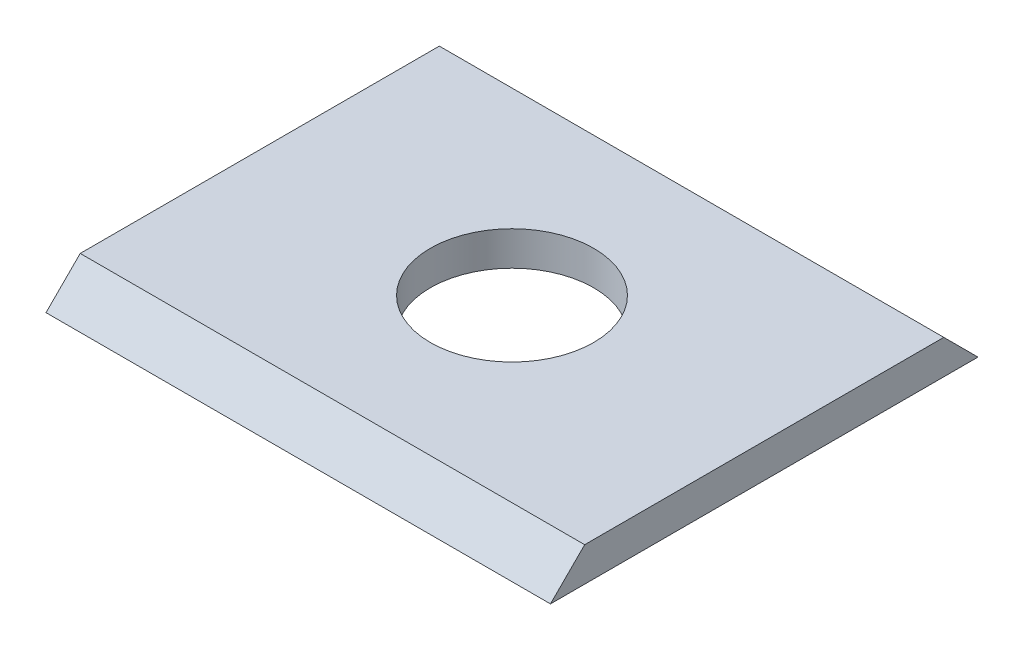
SolidWorks part; units mm, degrees
ref_plane "Front Plane" through (0, 0, 0) normal (0, 0, 1) x (1, 0, 0)
ref_plane "Top Plane" through (0, 0, 0) normal (0, 1, 0) x (1, 0, 0)
ref_plane "Right Plane" through (0, 0, 0) normal (1, 0, 0) x (0, 0, -1)
sketch "Sketch1" plane through (0, 0, 0) normal (0, 1, 0) x (1, 0, 0)
  line L0 (0, 0) -> (0, 50)
  line L1 (0, 0) -> (59, 0)
  line L2 (59, 0) -> (59, 50)
  line L3 (59, 50) -> (0, 50)
  line L4 (29.5, 50) -> (29.5, 25)
  circle A0 centre (29.5, 25) radius 9.55
extrude "Boss-Extrude1" add sketch "Sketch1" along normal blind 4 contours A0 L3 L0 L1 L2 region at (0.7734, 0, -25)
chamfer "Chamfer1" distance 4 angle 45 2 edges at (29.5, 4, -50) (29.5, 4, 0)
